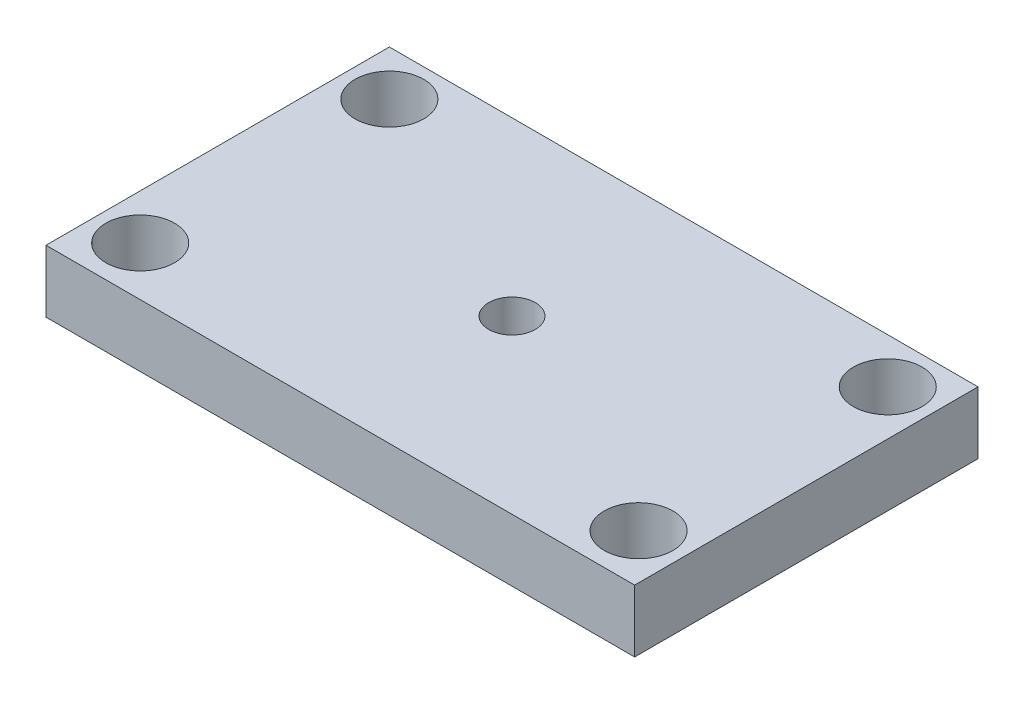
SolidWorks part; units mm, degrees
ref_plane "Front Plane" through (0, 0, 0) normal (0, 0, 1) x (1, 0, 0)
ref_plane "Top Plane" through (0, 0, 0) normal (0, 1, 0) x (1, 0, 0)
ref_plane "Right Plane" through (0, 0, 0) normal (1, 0, 0) x (0, 0, -1)
sketch "Sketch1" plane through (0, 0, 0) normal (0, 1, 0) x (1, 0, 0)
  line L0 (4.6, 30.4) -> (0, 30.4) construction
  line L1 (0, 0) -> (60, 0)
  line L2 (0, 0) -> (0, 35)
  line L3 (0, 35) -> (60, 35)
  line L4 (60, 0) -> (60, 35)
  line L5 (4.6, 30.4) -> (55.4, 30.4) construction
  line L6 (4.6, 30.4) -> (4.6, 5) construction
  line L7 (4.6, 5) -> (55.4, 5) construction
  line L8 (55.4, 30.4) -> (55.4, 5) construction
  line L9 (4.6, 30.4) -> (4.6, 35) construction
  circle A0 centre (4.6, 30.4) radius 3.5
  circle A1 centre (55.4, 30.4) radius 3.5
  circle A2 centre (4.6, 5) radius 3.5
  circle A3 centre (55.4, 5) radius 3.5
  circle A4 centre (30, 17.5) radius 2.375
  point P13 (30, 30.4)
  point P14 (30, 35)
  point P20 (60, 17.5)
  dimension "D5" = 7
  dimension "D6" = 4.75
  dimension "D1" = 60
  dimension "D2" = 35
  dimension "D3" = 50.8
  dimension "D4" = 25.4
extrude "Boss-Extrude1" add sketch "Sketch1" along normal blind 6.35
